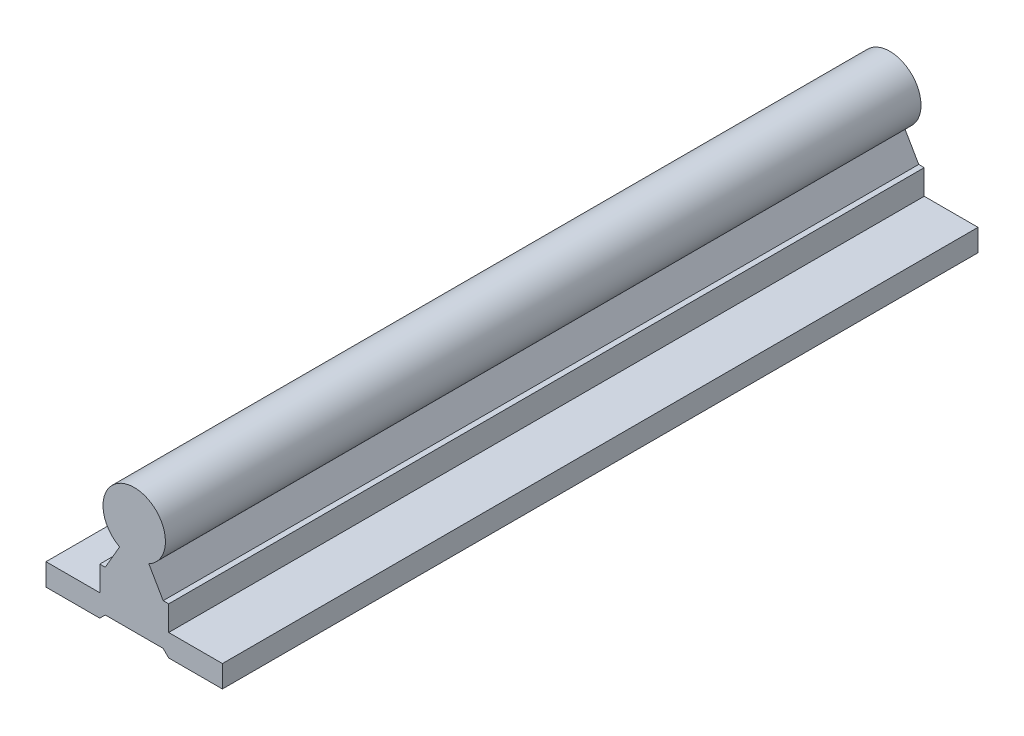
SolidWorks part; units mm, degrees
ref_plane "前视基准面" through (0, 0, 0) normal (0, 0, 1) x (1, 0, 0)
ref_plane "上视基准面" through (0, 0, 0) normal (0, 1, 0) x (1, 0, 0)
ref_plane "右视基准面" through (0, 0, 0) normal (1, 0, 0) x (0, 0, -1)
sketch "草图1" plane through (0, 0, 0) normal (0, 0, 1) x (1, 0, 0)
  line L0 (0, -207.286) -> (0, 10157.0132) construction
  line L1 (-16, 0) -> (16, 0)
  line L2 (-16, 0) -> (-16, 4)
  line L3 (-16, 4) -> (-6.25, 4)
  line L4 (-6.25, 4) -> (-6.25, 8.5)
  line L5 (6.25, 4) -> (16, 4)
  line L6 (16, 0) -> (16, 4)
  line L7 (6.25, 4) -> (6.25, 8.5)
  line L8 (-6.25, 8.5) -> (-5.25, 8.5)
  line L9 (6.25, 8.5) -> (5.25, 8.5)
  line L10 (-1000, 13) -> (49000, 13) construction
  line L11 (-2.6519, 13) -> (-5.25, 8.5)
  line L12 (5.25, 8.5) -> (2.6519, 13)
  arc A0 (-2.6519, 13) -> (2.6519, 13) centre (0, 18) cw
  dimension "D1" = 16
  dimension "D2" = 32
  dimension "D3" = 6.25
  dimension "D4" = 12.5
  dimension "D5" = 8.5
  dimension "D6" = 8.5
  dimension "D7" = 1
  dimension "D8" = 1
  dimension "D9" = 13
  dimension "D10" = 30
  dimension "D11" = 4
  dimension "D12" = 60
  dimension "D13" = 18
extrude "凸台-拉伸1" add sketch "草图1" along normal mid plane 137.04
sketch "草图2" plane through (0, 0, 68.52) normal (0, 0, 1) x (1, 0, 0)
  line L0 (-5.25, 0) -> (-5.25, 1)
  line L1 (-16, 0) -> (16, 0) construction
  line L2 (-5.25, 1) -> (5.25, 1)
  line L3 (5.25, 1) -> (5.25, 0)
  line L4 (-5.25, 0) -> (5.25, 0)
  dimension "D1" = 1
extrude "切除-拉伸1" cut sketch "草图2" against normal through all
chamfer "倒角1" distance 1 angle 45 2 edges at (5.25, 0, 0) (-5.25, 0, 0)
